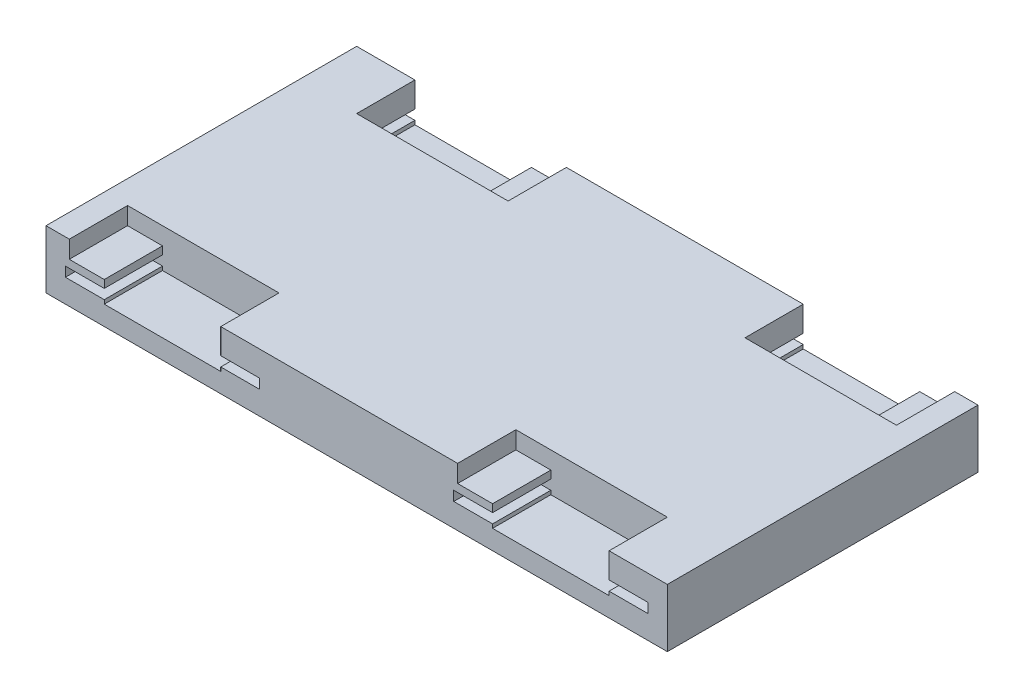
SolidWorks part; units mm, degrees
ref_plane "Front Plane" through (0, 0, 0) normal (0, 0, 1) x (1, 0, 0)
ref_plane "Top Plane" through (0, 0, 0) normal (0, 1, 0) x (1, 0, 0)
ref_plane "Right Plane" through (0, 0, 0) normal (1, 0, 0) x (0, 0, -1)
sketch "Sketch1" plane through (0, 0, 0) normal (0, 1, 0) x (1, 0, 0)
  line L1 (-160, 80) -> (160, 80)
  line L2 (-160, 80) -> (-160, -80)
  line L3 (-160, -80) -> (160, -80)
  line L4 (160, 80) -> (160, -80)
  line L5 (-160, 80) -> (160, -80) construction
  line L6 (-160, -80) -> (160, 80) construction
  point P0 (0, 0)
  dimension "D1" = 320
  dimension "D2" = 160
extrude "Boss-Extrude1" add sketch "Sketch1" along normal blind 20
sketch "Sketch2" plane through (0, 20, 0) normal (0, 1, 0) x (1, 0, 0)
  line L0 (-160, -80) -> (160, -80) construction
  line L1 (-130, -80) -> (-70, -80)
  line L2 (-130, -80) -> (-130, -50)
  line L3 (-130, -50) -> (-70, -50)
  line L4 (-70, -80) -> (-70, -50)
  line L5 (-160, 80) -> (-160, -80) construction
  dimension "D1" = 60
  dimension "D2" = 30
  dimension "D3" = 30
extrude "Cut-Extrude1" cut sketch "Sketch2" against normal blind 28
sketch "Sketch3" plane through (0, 0, 80) normal (0, 0, 1) x (1, 0, 0)
  line L0 (-130, 0) -> (-130, 20) construction
  line L1 (-130, 7) -> (-150, 7)
  line L2 (-130, 7) -> (-130, 2)
  line L3 (-130, 2) -> (-150, 2)
  line L4 (-150, 7) -> (-150, 2)
  line L5 (-160, 0) -> (-130, 0) construction
  line L6 (-70, 0) -> (-70, 20) construction
  line L7 (-70, 7) -> (-50, 7)
  line L8 (-70, 7) -> (-70, 2)
  line L9 (-70, 2) -> (-50, 2)
  line L10 (-50, 7) -> (-50, 2)
  line L11 (88, 0) -> (-88, 0) construction
  dimension "D1" = 2
  dimension "D2" = 5
  dimension "D3" = 20
  dimension "D4" = 20
  dimension "D5" = 5
  dimension "D6" = 2
extrude "Cut-Extrude3" cut sketch "Sketch3" against normal blind 30
mirror "Mirror2" about plane through (0, 0, 0) normal (1, 0, 0) of "Cut-Extrude1", "Cut-Extrude3"
mirror "Mirror3" about plane through (0, 0, 0) normal (0, 0, 1) of "Mirror2"
sketch "Sketch5" plane through (0, 0, 80) normal (0, 0, 1) x (1, 0, 0)
  line L0 (-130, 7) -> (-130, 20) construction
  line L1 (-130, 11) -> (-148, 11)
  line L2 (-130, 11) -> (-130, 20)
  line L3 (-130, 20) -> (-148, 20)
  line L4 (-148, 11) -> (-148, 20)
  line L5 (-160, 20) -> (-130, 20) construction
  line L6 (-130, 7) -> (-150, 7) construction
  dimension "D1" = 4
  dimension "D2" = 18
extrude "Cut-Extrude4" cut sketch "Sketch5" against normal blind 30
sketch "Sketch6" plane through (0, 0, 80) normal (0, 0, 1) x (1, 0, 0)
  line L0 (70, 7) -> (70, 20) construction
  line L1 (70, 11) -> (52, 11)
  line L2 (70, 11) -> (70, 20)
  line L3 (70, 20) -> (52, 20)
  line L4 (52, 11) -> (52, 20)
  line L5 (50, 7) -> (70, 7) construction
  dimension "D1" = 18
  dimension "D2" = 4
extrude "Cut-Extrude5" cut sketch "Sketch6" against normal blind 30
sketch "Sketch8" plane through (0, 0, -80) normal (0, 0, -1) x (-1, 0, 0)
  line L0 (-130, 7) -> (-130, 20) construction
  line L1 (-130, 11) -> (-148, 11)
  line L2 (-130, 11) -> (-130, 20)
  line L3 (-130, 20) -> (-148, 20)
  line L4 (-148, 11) -> (-148, 20)
  line L5 (-160, 20) -> (-130, 20) construction
  line L6 (-130, 7) -> (-150, 7) construction
  dimension "D1" = 18
  dimension "D2" = 4
extrude "Cut-Extrude6" cut sketch "Sketch8" against normal blind 30
sketch "Sketch9" plane through (0, 0, -80) normal (0, 0, -1) x (-1, 0, 0)
  line L0 (70, 20) -> (70, 7) construction
  line L1 (70, 11) -> (52, 11)
  line L2 (70, 11) -> (70, 20)
  line L3 (70, 20) -> (52, 20)
  line L4 (52, 11) -> (52, 20)
  line L5 (-70, 20) -> (70, 20) construction
  line L6 (50, 7) -> (70, 7) construction
  dimension "D1" = 18
  dimension "D2" = 4
extrude "Cut-Extrude7" cut sketch "Sketch9" against normal blind 30
sketch "Sketch10" plane through (0, 0, 0) normal (0, -1, 0) x (1, 0, 0)
  line L1 (-160, 80) -> (160, 80)
  line L2 (-160, 80) -> (-160, -80)
  line L3 (-160, -80) -> (160, -80)
  line L4 (160, 80) -> (160, -80)
extrude "Boss-Extrude2" add sketch "Sketch10" along normal blind 10
